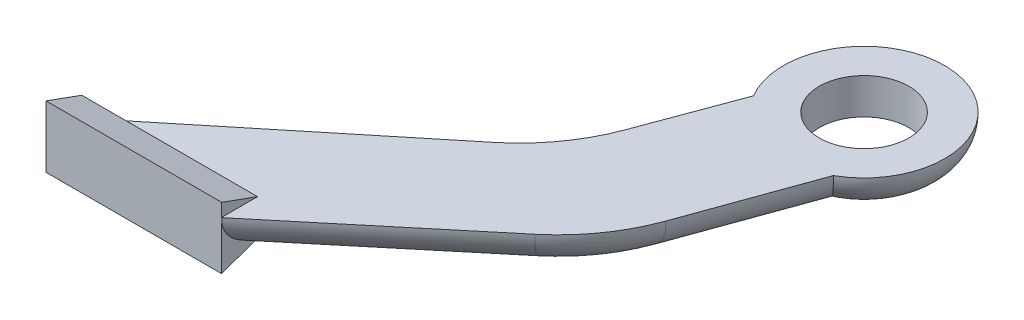
SolidWorks part; units mm, degrees
ref_plane "Front" through (0, 0, 0) normal (0, 0, 1) x (1, 0, 0)
ref_plane "Top" through (0, 0, 0) normal (0, 1, 0) x (1, 0, 0)
ref_plane "Right" through (0, 0, 0) normal (1, 0, 0) x (0, 0, -1)
sketch "Sketch1" plane through (0, 0, 0) normal (0, 1, 0) x (1, 0, 0)
  line L0 (4.7344, 4.3375) -> (-11.1234, -8.6004)
  line L1 (-11.1234, -8.6004) -> (-1.3192, -8.6004)
  line L2 (-1.3192, -8.6004) -> (10.2971, 1.0617)
  line L3 (10.2971, 1.0617) -> (13.6935, 10.4802)
  line L6 (-1.3192, -8.6004) -> (-1.3192, 14.3996) construction
  line L7 (-1.3192, 14.3996) -> (6.9826, 14.3996) construction
  line L9 (7.6119, 12.1045) -> (4.7344, 4.3375)
  circle A0 centre (11.4826, 14.3996) radius 2.5
  arc A1 (13.6935, 10.4802) -> (7.6119, 12.1045) centre (11.4826, 14.3996) ccw
  circle A2 centre (11.4826, 14.3996) radius 4.5 construction
  dimension "D1" = 2
extrude "Boss-Extrude1" add sketch "Sketch1" along normal blind 2
fillet "Fillet1" radius 10 1 edges at (10.2971, 1, -1.0617)
fillet "Fillet2" radius 10 1 edges at (4.7344, 1, -4.3375)
sketch "Sketch5" plane through (0, 0, 0) normal (1, 0, 0) x (0, 0, -1)
  line L0 (-8.6004, -0.725) -> (-8.6004, 2.725)
  line L5 (-6.6004, 0) -> (-8.6004, -0.725)
  line L6 (-8.6004, 1) -> (-6.6004, 1) construction
  line L7 (-6.6004, 0) -> (-6.6004, 2)
  line L8 (-6.6004, 2) -> (-8.6004, 2.725)
  line L14 (-8.6004, 2) -> (-8.6004, 0) construction
  point P9 (-8.6004, 1)
  point P12 (-6.6004, 1)
ref_plane "Plane1" through (-6.65, 0, 0) normal (1, 0, 0) x (0, 0, -1)
sketch "Sketch6" plane through (-6.65, 0, 0) normal (1, 0, 0) x (0, 0, -1)
  line L0 (-8.6004, 2.725) -> (-6.6004, 2)
  line L1 (-6.6004, 2) -> (-6.6004, 0)
  line L2 (-6.6004, 0) -> (-8.6004, -0.725)
  line L3 (-8.6004, -0.725) -> (-8.6004, 2.725)
extrude "Boss-Extrude2" add sketch "Sketch6" along normal blind 5.3 and the other way blind 4.5
fillet "Fillet7" radius 2 6 edges at (6.6461, 0, -9.4976) (4.4383, 0, -4.5492) (-3.0236, 0, 1.992) (12.4564, 0, -7.0496) (9.9999, 0, -1.2701) (3.4439, 0, 4.6385)
fillet "Fillet8" radius 2 1 edges at (12.7443, 0, -18.7191)
